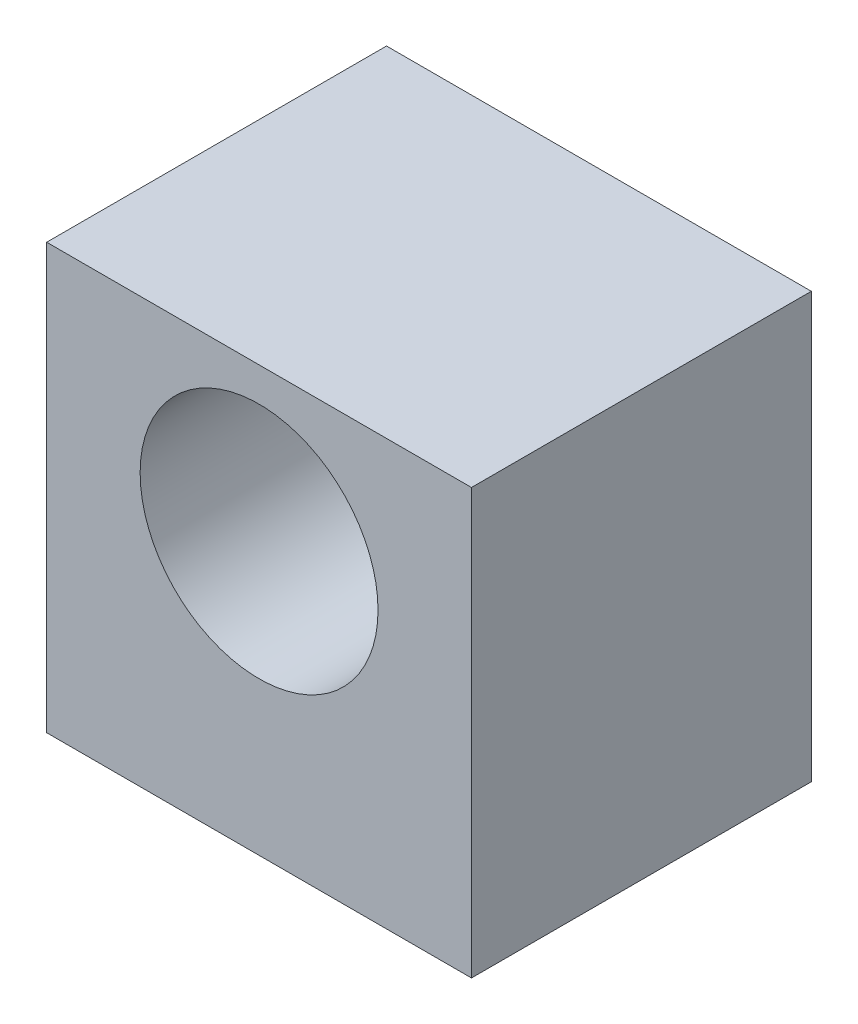
SolidWorks part; units mm, degrees
ref_plane "Front Plane" through (0, 0, 0) normal (0, 0, 1) x (1, 0, 0)
ref_plane "Top Plane" through (0, 0, 0) normal (0, 1, 0) x (1, 0, 0)
ref_plane "Right Plane" through (0, 0, 0) normal (1, 0, 0) x (0, 0, -1)
sketch "Sketch1" plane through (0, 0, 0) normal (0, 0, 1) x (1, 0, 0)
  line L1 (25, -25) -> (-25, -25)
  line L2 (25, -25) -> (25, 25)
  line L3 (25, 25) -> (-25, 25)
  line L4 (-25, -25) -> (-25, 25)
  line L5 (25, -25) -> (-25, 25) construction
  line L6 (25, 25) -> (-25, -25) construction
  point P0 (0, 0)
  dimension "D1" = 50
  dimension "D2" = 50
extrude "Boss-Extrude1" add sketch "Sketch1" against normal blind 40
sketch "Sketch2" plane through (0, 0, 0) normal (0, 0, 1) x (1, 0, 0)
  line L0 (0, 25) -> (0, -25) construction
  line L1 (25, 25) -> (-25, 25) construction
  line L2 (-25, -25) -> (25, -25) construction
  line L3 (-25, 7) -> (25, 7) construction
  line L4 (-25, 25) -> (-25, -25) construction
  line L5 (25, -25) -> (25, 25) construction
  circle A0 centre (0, 7) radius 14
  dimension "D1" = 28
  dimension "D2" = 18
extrude "Cut-Extrude1" cut sketch "Sketch2" against normal through all
sketch "Sketch3" plane through (0, 0, 0) normal (0, 0, 1) x (1, 0, 0)
  line L0 (0, 7) -> (13.435, 20.435) construction
  line L1 (0, 7) -> (19, 7) construction
  line L3 (0, 7) -> (0, -12) construction
  circle A0 centre (0, 7) radius 19 construction
  point P3 (-13.435, 20.435)
  point P7 (13.435, -6.435)
  point P8 (-13.435, -6.435)
  dimension "D1" = 38
  dimension "D2" = 45
sketch "Sketch4" plane through (0, -25, 0) normal (0, -1, 0) x (1, 0, 0)
  line L0 (0, 0) -> (0, -40) construction
  line L1 (19, 0) -> (-19, 0) construction
  line L2 (-25, -40) -> (25, -40) construction
  line L3 (-25, -20) -> (25, -20) construction
  line L4 (-25, -40) -> (-25, 0) construction
  line L5 (25, -40) -> (25, 0) construction
  point P12 (-10, -10)
  point P13 (10, -10)
  point P14 (10, -30)
  point P15 (-10, -30)
  dimension "D1" = 10
  dimension "D2" = 10
hole_wizard "M5 Tapped Hole1" positions "3DSketch1" profile "Sketch6" tap size "M5" standard "ISO"
sketch3d "3DSketch1"
  point P0 (-10, -25, -10)
  point P3 (10, -25, -10)
  point P6 (10, -25, -30)
  point P9 (-10, -25, -30)
sketch "Sketch6" plane through (-10, -25, -10) normal (1, 0, 0) x (0, 0, -1)
  line L0 (0, 0) -> (0, 16.2618)
  line L1 (0, 16.2618) -> (2.1, 15)
  line L2 (2.1, 15) -> (2.1, 0)
  line L5 (2.1, 0) -> (0, 0)
  line L10 (0, 16.2618) -> (-2.1, 15) construction
  line L11 (0, -6.35) -> (0, 107.95) construction
  dimension "Tap Drill Dia." = 4.2
  dimension "Tap Drill Depth" = 15
  dimension "Drill Angle" = 118
cosmetic thread "Hole Thread1" parameters "D1"=14.5, "D2"=5
cosmetic thread "Hole Thread2" parameters "D1"=14.5, "D2"=5
cosmetic thread "Hole Thread3" parameters "D1"=14.5, "D2"=5
cosmetic thread "Hole Thread4" parameters "D1"=14.5, "D2"=5
